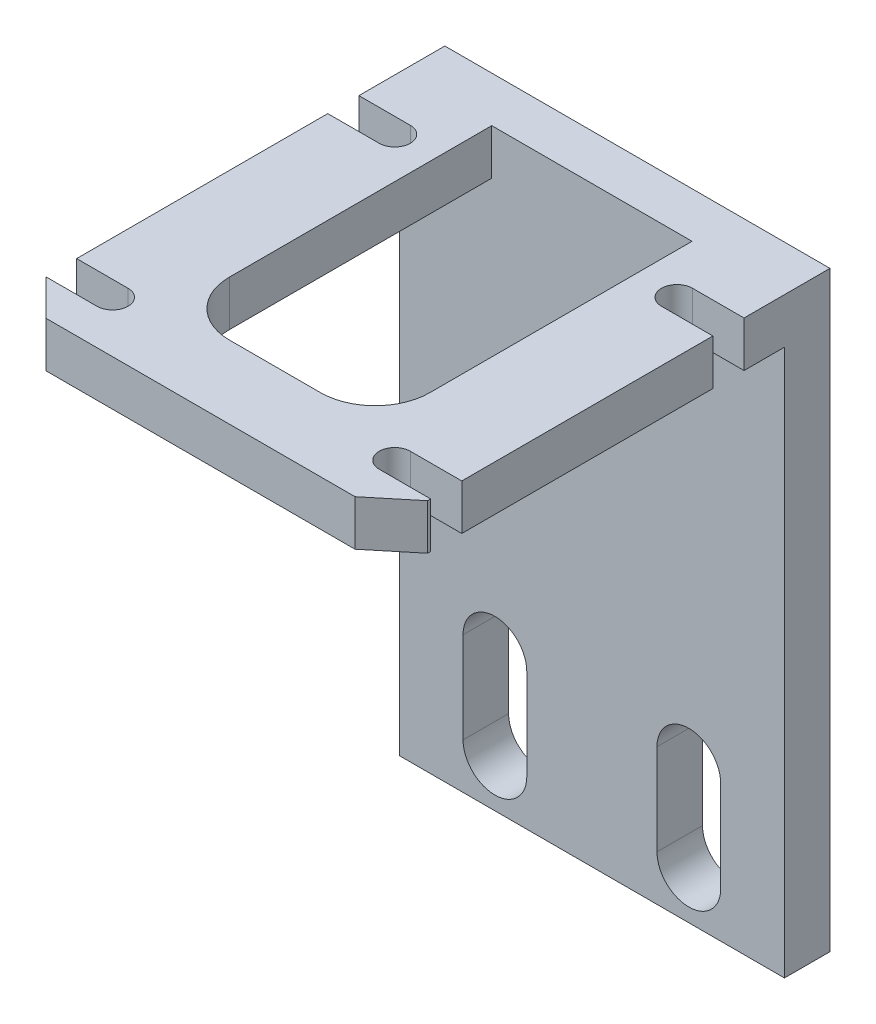
SolidWorks part; units mm, degrees
ref_plane "Front Plane" through (0, 0, 0) normal (0, 0, 1) x (1, 0, 0)
ref_plane "Top Plane" through (0, 0, 0) normal (0, 1, 0) x (1, 0, 0)
ref_plane "Right Plane" through (0, 0, 0) normal (1, 0, 0) x (0, 0, -1)
sketch "Sketch1" plane through (0, 0, 0) normal (0, 1, 0) x (1, 0, 0)
  line L1 (-10.2553, 3.0084) -> (11.7447, 3.0084)
  line L2 (-20.4053, 3.0084) -> (-20.4053, -4.9916)
  line L3 (-20.4053, -4.9916) -> (21.8947, -4.9916)
  line L4 (21.8947, 3.0084) -> (21.8947, -4.9916)
  line L5 (0, 0) -> (21.8947, -4.9916) construction
  line L6 (-20.4053, -4.9916) -> (0, 0) construction
  line L8 (-20.4053, 3.0084) -> (-20.4053, 42.8084)
  line L9 (-20.4053, 42.8084) -> (-10.2553, 42.8084)
  line L10 (-10.2553, 3.0084) -> (-10.2553, 42.8084)
  line L12 (21.8947, 3.0084) -> (21.8947, 42.8084)
  line L13 (21.8947, 42.8084) -> (11.7447, 42.8084)
  line L14 (11.7447, 3.0084) -> (11.7447, 42.8084)
  point P0 (0, 0)
  dimension "D1" = 42.3
  dimension "D2" = 47.8
  dimension "D3" = 22
  dimension "D4" = 8
  dimension "D5" = 4.9916
extrude "Boss-Extrude1" add sketch "Sketch1" along normal blind 5
sketch "Sketch2" plane through (0, 0, 0) normal (0, -1, 0) x (1, 0, 0)
  line L0 (-20.4053, -33.3684) -> (-14.7553, -33.3684)
  line L1 (-20.4053, 4.9916) -> (21.8947, 4.9916) construction
  line L2 (21.8947, 4.9916) -> (21.8947, -42.8084) construction
  line L3 (-20.4053, -29.9484) -> (-14.7553, -29.9484)
  line L4 (-20.4053, -2.3684) -> (-14.7553, -2.3684)
  line L5 (-20.4053, 1.0516) -> (-14.7553, 1.0516)
  line L6 (21.8947, 1.0516) -> (16.2447, 1.0516)
  line L7 (21.8947, -2.3684) -> (16.2447, -2.3684)
  line L8 (21.8947, -29.9484) -> (16.2447, -29.9484)
  line L9 (21.8947, -33.3684) -> (16.2447, -33.3684)
  line L10 (-20.4053, -42.8084) -> (-20.4053, 4.9916) construction
  line L11 (21.8947, 4.9916) -> (21.8947, -42.8084) construction
  line L12 (-20.4053, -33.3684) -> (-20.4053, -29.9484)
  line L13 (21.8947, 1.0516) -> (21.8947, -2.3684)
  line L14 (21.8947, -29.9484) -> (21.8947, -33.3684)
  line L15 (-20.4053, -2.3684) -> (-20.4053, 1.0516)
  arc A0 (-14.7553, -33.3684) -> (-14.7553, -29.9484) centre (-14.7553, -31.6584) ccw
  arc A1 (-14.7553, -2.3684) -> (-14.7553, 1.0516) centre (-14.7553, -0.6584) ccw
  arc A2 (16.2447, 1.0516) -> (16.2447, -2.3684) centre (16.2447, -0.6584) ccw
  arc A3 (16.2447, -29.9484) -> (16.2447, -33.3684) centre (16.2447, -31.6584) ccw
  dimension "D5" = 3.42
  dimension "D1" = 31
  dimension "D2" = 31
  dimension "D3" = 5.65
  dimension "D4" = 5.65
extrude "Cut-Extrude1" cut sketch "Sketch2" against normal through all
fillet "Fillet1" radius 6 2 edges at (-10.2553, 2.5, -3.0084) (11.7447, 2.5, -3.0084)
sketch "Sketch3" plane through (0, 0, 0) normal (0, -1, 0) x (1, 0, 0)
  line L0 (21.8947, 1.3913) -> (17.5274, 4.9916)
  line L1 (21.8947, 4.9916) -> (21.8947, 1.0516) construction
  line L2 (-20.4053, 4.9916) -> (21.8947, 4.9916) construction
  line L3 (17.5274, 4.9916) -> (21.8947, 4.9916)
  line L4 (21.8947, 4.9916) -> (21.8947, 1.3913)
  line L5 (-20.4053, 0.9947) -> (-16.3978, 4.9916)
  line L6 (-20.4053, -42.8084) -> (-20.4053, -33.3684) construction
  line L7 (-16.3978, 4.9916) -> (-20.4053, 4.9916)
  line L8 (-20.4053, 4.9916) -> (-20.4053, 0.9947)
  dimension "D1" = 5.66
extrude "Cut-Extrude2" cut sketch "Sketch3" against normal through all
sketch "Sketch5" plane through (0, 5, 0) normal (0, 1, 0) x (1, 0, 0)
  line L0 (21.8947, 42.8084) -> (-10.2553, 42.8084)
  line L1 (21.8947, 42.8084) -> (21.8947, 37.8084)
  line L3 (21.8947, 37.8084) -> (-10.2553, 37.8084)
  line L4 (-10.2553, 42.8084) -> (-20.4053, 42.8084)
  line L6 (-20.4053, 42.8084) -> (-20.4053, 37.8084)
  line L7 (-10.2553, 37.8084) -> (-20.4053, 37.8084)
extrude "Boss-Extrude4" add sketch "Sketch5" against normal blind 65
fillet "Fillet2" [suppressed] radius 1
sketch "Sketch7" plane through (0, 0, -37.8084) normal (0, 0, 1) x (1, 0, 0)
  line L0 (-9.9053, -45) -> (-9.9053, -55) construction
  line L1 (-6.4053, -45) -> (-6.4053, -55)
  line L2 (-13.4053, -45) -> (-13.4053, -55)
  line L3 (11.3947, -45) -> (11.3947, -55) construction
  line L4 (14.8947, -45) -> (14.8947, -55)
  line L5 (7.8947, -45) -> (7.8947, -55)
  line L6 (-20.4053, -60) -> (21.8947, -60) construction
  line L7 (-20.4053, -60) -> (-20.4053, 0) construction
  line L9 (21.8947, -60) -> (21.8947, 0) construction
  arc A0 (-6.4053, -45) -> (-13.4053, -45) centre (-9.9053, -45) ccw
  arc A1 (-13.4053, -55) -> (-6.4053, -55) centre (-9.9053, -55) ccw
  arc A2 (14.8947, -45) -> (7.8947, -45) centre (11.3947, -45) ccw
  arc A3 (7.8947, -55) -> (14.8947, -55) centre (11.3947, -55) ccw
  point P2 (-9.9053, -50)
  point P9 (11.3947, -50)
  dimension "D3" = 3.5
  dimension "D6" = 3.5
  dimension "D1" = 5
  dimension "D2" = 15
  dimension "D4" = 7
  dimension "D5" = 7
  dimension "D7" = 5
  dimension "D8" = 15
extrude "Cut-Extrude4" cut sketch "Sketch7" against normal through all
equation "\"26..50mm\"=27"
